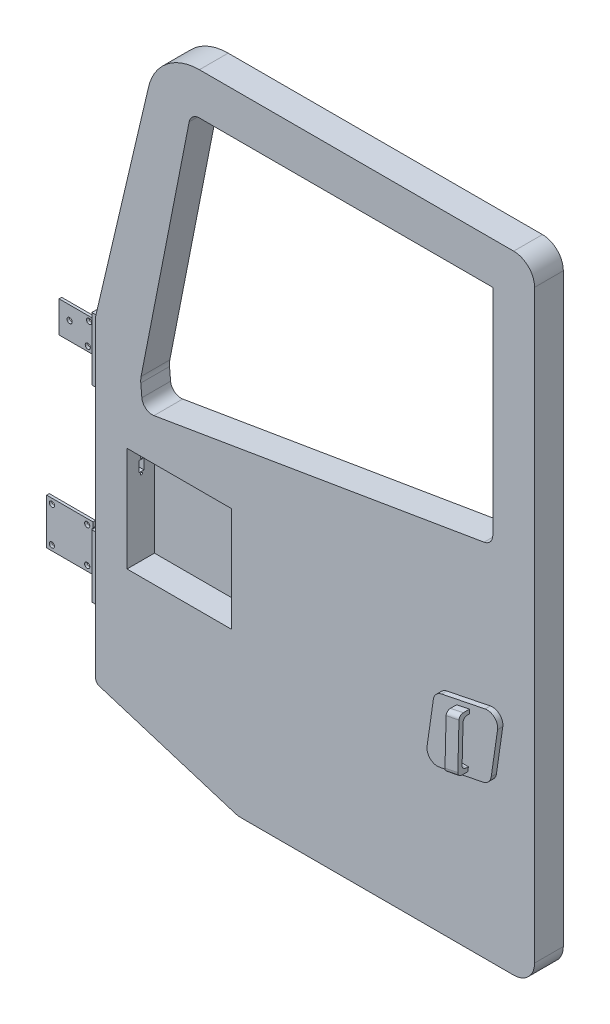
SolidWorks part; units mm, degrees
ref_plane "Front Plane" through (0, 0, 0) normal (0, 0, 1) x (1, 0, 0)
ref_plane "Top Plane" through (0, 0, 0) normal (0, 1, 0) x (1, 0, 0)
ref_plane "Right Plane" through (0, 0, 0) normal (1, 0, 0) x (0, 0, -1)
sketch "Sketch2" plane through (0, 0, 0) normal (0, 0, 1) x (1, 0, 0)
  line L1 (-179.7693, -762.022) -> (482.6, -762.022)
  line L3 (-281.2299, 761.978) -> (482.6, 761.978)
  line L4 (533.4, -711.222) -> (533.4, 711.178)
  line L5 (-459.8603, -656.939) -> (-452.0517, -645.784) construction
  line L6 (-417.9715, 597.0829) -> (44.2876, -63.266) construction
  line L8 (-524.4721, -657.2008) -> (-194.8579, -759.7295)
  line L9 (-306.1723, 639.7777) -> (-423.0219, 45.4039)
  line L10 (-423.7768, 31.1096) -> (-421.1458, 1.4921)
  line L14 (-281.2299, 660.378) -> (431.8, 660.378)
  line L16 (431.7996, 138.4174) -> (431.8, 660.378)
  line L17 (431.8, -660.422) -> (431.8, 660.378) construction
  line L18 (-172.0509, -660.422) -> (431.8, -660.422) construction
  line L19 (-533.4, 116.926) -> (-405.8883, 659.253)
  line L20 (-367.7549, -599.547) -> (-172.0509, -660.422) construction
  line L21 (-55.7209, -79.6007) -> (521.0599, 744.3665) construction
  line L22 (-306.1723, 639.7777) -> (-424.4164, 38.3105) construction
  line L23 (-424.4164, 38.3105) -> (-367.7549, -599.547) construction
  line L24 (-414.3579, -691.4526) -> (-194.8579, -759.7295) construction
  line L25 (-179.7693, -762.022) -> (482.6, -762.022)
  line L27 (-281.2299, 761.978) -> (482.6, 761.978)
  line L28 (533.4, -711.222) -> (533.4, 711.178)
  line L29 (-459.8603, -656.939) -> (-452.0517, -645.784) construction
  line L30 (-417.9715, 597.0829) -> (44.2876, -63.266) construction
  line L31 (-533.4, 116.926) -> (-466.2749, -638.723) construction
  line L32 (-391.6402, -21.3099) -> (410.6048, 113.3679)
  line L33 (-55.7209, -79.6007) -> (521.0599, 744.3665) construction
  line L34 (-281.2299, 761.978) -> (482.6, 761.978)
  line L35 (-533.4, 116.926) -> (-533.4, -645.074)
  line L36 (-179.7693, -762.022) -> (482.6, -762.022)
  line L37 (533.4, 711.178) -> (533.4, -711.222)
  line L38 (-417.9715, 597.0829) -> (44.2876, -63.266) construction
  line L39 (-471.5639, -673.6583) -> (-452.0517, -645.784) construction
  line L40 (-405.8883, 659.253) -> (-528.8132, 33.9764) construction
  line L41 (-55.7209, -79.6007) -> (521.0599, 744.3665) construction
  arc A0 (-405.8883, 659.253) -> (-281.2299, 761.978) centre (-281.2299, 634.978) cw
  arc A3 (533.4, 711.178) -> (482.6, 761.978) centre (482.6, 711.178) ccw
  arc A4 (482.6, -762.022) -> (533.4, -711.222) centre (482.6, -711.222) ccw
  arc A5 (-194.8579, -759.7295) -> (-179.7693, -762.022) centre (-179.7693, -711.222) ccw
  arc A7 (-367.7549, -599.547) -> (-367.7549, -599.547) centre (-367.7549, -599.547) ccw
  arc A8 (-172.0509, -660.422) -> (-172.0509, -660.422) centre (-172.0509, -660.422) ccw
  arc A9 (431.8, -660.422) -> (431.8, -660.422) centre (431.8, -660.422) ccw
  arc A10 (431.8, 660.378) -> (431.8, 660.378) centre (431.8, 660.378) ccw
  arc A11 (-306.1723, 639.7777) -> (-281.2299, 660.378) centre (-281.2299, 634.978) cw
  arc A12 (-423.0219, 45.4039) -> (-423.7768, 31.1096) centre (-373.176, 35.6045) ccw
  arc A13 (-424.4164, 38.3105) -> (-424.4164, 38.3105) centre (-424.4164, 38.3105) ccw construction
  arc A16 (-466.2749, -638.723) -> (-414.3579, -691.4526) centre (-391.0208, -616.5518) ccw construction
  arc A17 (-533.4, -645.074) -> (-524.4721, -657.2008) centre (-520.7, -645.074) ccw
  arc A18 (-528.8132, 33.9764) -> (-533.4, 116.926) centre (-501.9071, 77.0658) ccw construction
  arc A19 (431.7996, 138.4174) -> (410.6048, 113.3679) centre (406.3996, 138.4174) cw
  arc A20 (-391.6402, -21.3099) -> (-421.1458, 1.4921) centre (-395.8454, 3.7395) cw
  point P0 (0, 0)
  point P16 (-533.4, -0.0244)
  point P56 (0, 0)
  point P61 (0, 0)
  dimension "D3" = 127
  dimension "D6" = 50.8
  dimension "D8" = 50.8
  dimension "D2" = 12.7
  dimension "D9" = 25.4
  dimension "D1" = 1066.8
  dimension "D4" = 1524
  dimension "D5" = 762
  dimension "D7" = 101.6
extrude "Boss-Extrude1" add sketch "Sketch2" along normal mid plane 69.85 contours L8 A5 L1 A4 L4 A3 L3 A0 L10 A12 L9 A11 L14 L16 A20 region at (22.1716, -171.0663, 0)
ref_plane "bottom" through (0, -762.022, 0) normal (0, -1, 0) x (-1, 0, 0)
ref_plane "top door check" through (0, -158.772, 0) normal (0, -1, 0) x (-1, 0, 0)
ref_plane "door check mid" through (0, -176.2345, 0) normal (0, -1, 0) x (-1, 0, 0)
ref_plane "bottom door check" through (0, -193.697, 0) normal (0, -1, 0) x (-1, 0, 0)
ref_plane "top hinge top hole" through (0, 66.653, 0) normal (0, -1, 0) x (-1, 0, 0)
ref_plane "top hinge middle hole" through (0, 44.428, 0) normal (0, -1, 0) x (-1, 0, 0)
ref_plane "top hinge bottom hole" through (0, 12.678, 0) normal (0, -1, 0) x (-1, 0, 0)
ref_plane "bottome hinge top hole" through (0, -363.5595, 0) normal (0, -1, 0) x (-1, 0, 0)
ref_plane "bottom hinge bottom hole" through (0, -449.2845, 0) normal (0, -1, 0) x (-1, 0, 0)
ref_plane "Plane1" through (0, 0, 31.75) normal (0, 0, 1) x (1, 0, 0)
sketch "Sketch3" plane through (0, 0, 34.925) normal (0, 0, 1) x (1, 0, 0)
  line L0 (320.1959, -245.101) -> (425.9265, -223.6716)
  line L3 (314.9201, -401.6691) -> (420.6507, -380.2397)
  line L4 (456.113, -252.1835) -> (440.7462, -358.9639)
  line L5 (300.1004, -266.3768) -> (284.7336, -373.1572)
  line L6 (310.4001, -194.8067) -> (287.3499, -354.9772) construction
  line L7 (-487.6326, -408.8312) -> (533.4008, -201.8888) construction
  line L8 (-457.3598, -558.1943) -> (563.6737, -351.2518) construction
  line L9 (461.2461, -216.515) -> (438.1959, -376.6855) construction
  line L10 (373.0612, -234.3863) -> (367.7854, -390.9544) construction
  line L11 (360.2667, -236.9795) -> (354.9908, -393.5476)
  line L12 (385.8558, -231.7931) -> (380.58, -388.3612)
  line L13 (360.3684, -233.9586) -> (355.0926, -390.5267) construction
  line L14 (385.754, -234.814) -> (380.4782, -391.3821) construction
  arc A0 (300.1004, -266.3768) -> (320.1959, -245.101) centre (325.2414, -269.9949) cw
  arc A1 (284.7336, -373.1572) -> (314.9201, -401.6691) centre (309.8746, -376.7752) ccw
  arc A2 (440.7462, -358.9639) -> (420.6507, -380.2397) centre (415.6052, -355.3458) cw
  arc A3 (456.113, -252.1835) -> (425.9265, -223.6716) centre (430.972, -248.5655) ccw
  dimension "D3" = 25.4
  dimension "D1" = 152.4
  dimension "D2" = 152.4
  dimension "D4" = 12.7
  dimension "D5" = 12.7
extrude "Boss-Extrude2" add sketch "Sketch3" along normal blind 12.7 contours L5 A1 L3 L11 L0 A0 | L4 A3 L0 L12 L3 A2 | L12 L0 L11 L3 region at (325.2101, -323.7797, 34.925) region at (370.4233, -312.6704, 34.925) region at (415.6365, -301.561, 34.925)
sketch "Sketch5" plane through (0, 0, 34.925) normal (0, 0, 1) x (1, 0, 0)
  line L6 (-179.7693, -762.022) -> (482.6, -762.022)
  line L12 (-179.7693, -762.022) -> (482.6, -762.022)
  line L28 (387.9598, -243.0291) -> (384.7172, -375.8602)
  line L29 (353.4927, -382.1888) -> (356.7353, -249.3577)
  line L30 (387.9598, -243.0291) -> (356.7353, -249.3577)
  line L31 (384.7172, -375.8602) -> (353.4927, -382.1888)
  line L32 (320.1959, -245.101) -> (425.9265, -223.6716) construction
  line L33 (314.9201, -401.6691) -> (420.6507, -380.2397) construction
  line L34 (320.1959, -245.101) -> (425.9265, -223.6716) construction
  line L35 (314.9201, -401.6691) -> (420.6507, -380.2397) construction
  dimension "D2" = 11.43
  dimension "D3" = 11.43
  dimension "D1" = 0
extrude "Boss-Extrude4" add sketch "Sketch5" along normal blind 38.1 contours L31 L28 L30 L29 region at (370.7262, -312.609, 34.925)
sketch "Sketch6" plane through (393.6581, -9.61, 0) normal (0.9997, -0.0244, 0) x (0, 0, -1)
  line L9 (-47.625, -356.1994) -> (-62.865, -356.1994)
  line L10 (-62.865, -356.1994) -> (-62.865, -243.6487)
  line L11 (-62.865, -243.6487) -> (-47.625, -243.6487)
  line L12 (-47.625, -356.1994) -> (-62.865, -356.1994)
  line L13 (-62.865, -356.1994) -> (-62.865, -243.6487)
  line L14 (-62.865, -243.6487) -> (-47.625, -243.6487)
  line M5 (-47.625, -366.3594) -> (-47.625, -233.4887)
  dimension "D1" = 10.16
extrude "Cut-Extrude6" cut sketch "Sketch6" against normal through all and the other way through all contours L14 L13 L12 M5 region at (386.3385, -309.4447, 55.245)
fillet "Fillet5" radius 10.16 4 edges at (369.1049, -379.0245, 73.025) (369.4394, -365.3242, 62.865) (372.1861, -252.8071, 62.865) (372.3476, -246.1934, 73.025)
sketch "Sketch7" plane through (-533.4, 59.3738, 0) normal (1, 0, 0) x (0, 0, 1)
  line L0 (0, 821.3958) -> (0, -702.6042) construction
  line L1 (34.925, 821.3958) -> (-34.925, 821.3958) construction
  line L2 (34.925, -702.6042) -> (-34.925, -702.6042) construction
  line L4 (-31.75, -57.5522) -> (31.75, -57.5522)
  line L5 (-31.75, -57.5522) -> (-31.75, 94.8478)
  line L6 (-31.75, 94.8478) -> (31.75, 94.8478)
  line L11 (31.75, -57.5522) -> (31.75, 94.8478)
  line L12 (-31.75, -57.5522) -> (31.75, 94.8478) construction
  line L13 (-31.75, 94.8478) -> (31.75, -57.5522) construction
  line L19 (34.925, -57.5522) -> (-34.925, -57.5522) construction
  line L21 (-31.75, 552.0478) -> (31.75, 552.0478)
  line L28 (-31.75, 552.0478) -> (-31.75, 399.6478)
  line L29 (-31.75, 399.6478) -> (31.75, 399.6478)
  line L30 (31.75, 552.0478) -> (31.75, 399.6478)
  line L31 (-31.75, 552.0478) -> (31.75, 399.6478) construction
  line L32 (-31.75, 399.6478) -> (31.75, 552.0478) construction
  point P6 (0, 18.6478)
  point P13 (0, 475.8478)
  dimension "D1" = 63.5
  dimension "D2" = 152.4
  dimension "D4" = 304.8
extrude "Boss-Extrude5" add sketch "Sketch7" against normal blind 12.7
sketch "Sketch16" plane through (0, 0, 34.925) normal (0, 0, 1) x (1, 0, 0)
  line L1 (-457.2, -122.9099) -> (-457.2, -376.9099)
  line L3 (-203.2, -376.9099) -> (-203.2, -122.9099)
  line L5 (-533.4, 116.926) -> (-533.4, -645.074) construction
  line L6 (-457.2, -122.9099) -> (-203.2, -122.9099)
  line L7 (-457.2, -376.9099) -> (-203.2, -376.9099)
  dimension "D1" = 254
  dimension "D2" = 101.6
  dimension "D3" = 254
  dimension "D4" = 76.2
extrude "Cut-Extrude8" cut sketch "Sketch16" against normal blind 66.675
sketch "Sketch20" plane through (-533.4, 0, 0) normal (-1, 0, 0) x (0, 0, 1)
  line L0 (-38.4175, -176.2345) -> (38.4175, -176.2345) construction
  line L1 (-6.35, -188.9345) -> (6.35, -188.9345)
  line L2 (-6.35, -188.9345) -> (-6.35, -163.5345)
  line L3 (-6.35, -163.5345) -> (6.35, -163.5345)
  line L4 (6.35, -188.9345) -> (6.35, -163.5345)
  line L5 (-6.35, -188.9345) -> (6.35, -163.5345) construction
  line L6 (-6.35, -163.5345) -> (6.35, -188.9345) construction
  line L7 (-38.4175, -158.772) -> (38.4175, -158.772) construction
  line L8 (6.35, -176.2345) -> (-6.35, -176.2345) construction
  circle A0 centre (0, -158.772) radius 2.54
  circle A1 centre (0, -193.697) radius 2.54
  point P0 (0, -176.2345)
  dimension "D3" = 5.08
  dimension "D1" = 12.7
  dimension "D2" = 25.4
extrude "Cut-Extrude12" cut sketch "Sketch20" against normal up to surface (76.2 mm away) contours A0 | L4 L3 L2 L1 | A1 up to face at (-457.2, -249.9099, 1.5875)
sketch "Sketch21" plane through (0, 0, 0) normal (0, 0, 1) x (1, 0, 0)
  line L0 (-38.4175, 66.653) -> (38.4175, 66.653) construction
  line L1 (-202.423, 66.653) -> (-1027.3811, 66.653) construction
  line L2 (-212.5576, 44.428) -> (-1027.3811, 44.428) construction
  line L3 (-38.4175, 44.428) -> (38.4175, 44.428) construction
  line L4 (-212.5576, 12.678) -> (-1027.3811, 12.678) construction
  line L5 (-38.4175, 12.678) -> (38.4175, 12.678) construction
  line L6 (-546.1, 116.926) -> (-546.1, -35.474) construction
  line L7 (-558.8, 66.653) -> (-546.1, 66.653)
  line L8 (-558.8, 66.653) -> (-558.8, 12.678)
  line L9 (-558.8, 12.678) -> (-546.1, 12.678)
  line L10 (-546.1, 66.653) -> (-546.1, 12.678)
  line L11 (-654.05, 77.448) -> (-654.05, 1.248)
  line L12 (-654.05, 77.448) -> (-558.8, 77.448)
  line L15 (-558.8, 77.448) -> (-558.8, 12.678)
  line L16 (-654.05, 77.448) -> (-558.8, 12.678) construction
  line L17 (-654.05, 10.0872) -> (-558.8, 77.448) construction
  line L18 (-654.05, 1.248) -> (-558.8, 1.248)
  line L19 (-558.8, 12.678) -> (-558.8, 1.248)
  circle A0 centre (-584.2, 12.678) radius 6.35
  circle A1 centre (-628.65, 44.428) radius 6.35
  circle A2 centre (-581.025, 66.653) radius 6.35
  point P18 (-605.4912, 44.428)
  dimension "D2" = 12.7
  dimension "D3" = 25.4
  dimension "D4" = 69.85
  dimension "D5" = 22.225
  dimension "D6" = 95.25
  dimension "D9" = 64.77
  dimension "D1" = 12.7
  dimension "D7" = 76.2
  dimension "D8" = 33.02
extrude "Boss-Extrude8" add sketch "Sketch21" along normal mid plane 6.35 contours L19 L8 L15 L12 L11 L18 A2 A1 A0 | L10 L7 L8 L9 region at (-552.45, 39.6655, 0) region at (-606.8928, 39.2427, 0)
sketch "Sketch26" plane through (0, 0, 0) normal (0, 0, 1) x (1, 0, 0)
  line L0 (-193.6896, -363.5595) -> (-881.8717, -363.5595) construction
  line L1 (-38.4175, -363.5595) -> (38.4175, -363.5595) construction
  line L2 (-133.4597, -449.2845) -> (-881.8717, -449.2845) construction
  line L3 (-38.4175, -449.2845) -> (38.4175, -449.2845) construction
  line L4 (-625.8948, -363.5595) -> (-625.8948, -449.2845) construction
  line L5 (-625.8948, -406.422) -> (-892.4677, -406.422) construction
  line L6 (-546.1, -340.274) -> (-546.1, -492.674) construction
  line L7 (-571.5, -449.2845) -> (-546.1, -449.2845)
  line L8 (-571.5, -449.2845) -> (-571.5, -363.5595)
  line L9 (-571.5, -363.5595) -> (-546.1, -363.5595)
  line L10 (-546.1, -449.2845) -> (-546.1, -363.5595)
  line L11 (-571.5, -449.2845) -> (-546.1, -363.5595) construction
  line L12 (-571.5, -363.5595) -> (-546.1, -449.2845) construction
  point P12 (-558.8, -406.422)
  dimension "D1" = 25.4
extrude "Boss-Extrude12" add sketch "Sketch26" along normal mid plane 12.7
sketch "Sketch27" plane through (0, 0, 0) normal (0, 0, 1) x (1, 0, 0)
  line L0 (-211.2814, -363.5595) -> (-919.4505, -363.5595) construction
  line L1 (-38.4175, -363.5595) -> (38.4175, -363.5595) construction
  line L2 (-201.3631, -449.2845) -> (-928.7076, -449.2845) construction
  line L3 (-38.4175, -449.2845) -> (38.4175, -449.2845) construction
  line L4 (-571.5, -363.5595) -> (-571.5, -449.2845) construction
  line L5 (-631.7994, -363.5595) -> (-631.7994, -449.2845) construction
  line L6 (-631.7994, -406.422) -> (-919.4505, -406.422) construction
  line L8 (-684.2125, -461.9845) -> (-571.5, -461.9845)
  line L9 (-684.2125, -461.9845) -> (-684.2125, -350.8595)
  line L10 (-684.2125, -350.8595) -> (-571.5, -350.8595)
  line L11 (-571.5, -461.9845) -> (-571.5, -350.8595)
  line L12 (-684.2125, -461.9845) -> (-571.5, -350.8595) construction
  line L13 (-684.2125, -350.8595) -> (-571.5, -461.9845) construction
  circle A0 centre (-585.7875, -363.5595) radius 6.35
  circle A2 centre (-671.5125, -449.2845) radius 6.35
  circle A4 centre (-585.7875, -449.2845) radius 6.35
  circle A5 centre (-671.5125, -363.5595) radius 6.35
  point P22 (-627.8563, -406.422)
  dimension "D1" = 12.7
  dimension "D2" = 100.0125
  dimension "D3" = 14.2875
  dimension "D4" = 12.7
extrude "Boss-Extrude13" add sketch "Sketch27" along normal mid plane 6.35
equation "\"doorwidth\"= 42in"
equation "\"D1@Sketch2\"=\"doorwidth\""
equation "\"doorheight\"= 60in"
equation "\"D4@Sketch2\"=\"doorheight\""
equation "\"doorthickness\"= 2.75in"
equation "\"D1@Boss-Extrude1\"=\"doorthickness\""
equation "\"hingewidth\"= 2.5in"
equation "\"hingeheight\"= 6in"
equation "\"distanceofhinges\"= 12in"
equation "\"D1@Sketch7\"=\"hingewidth\""
equation "\"D2@Sketch7\"=\"hingeheight\""
equation "\"D4@Sketch7\"=\"distanceofhinges\""
